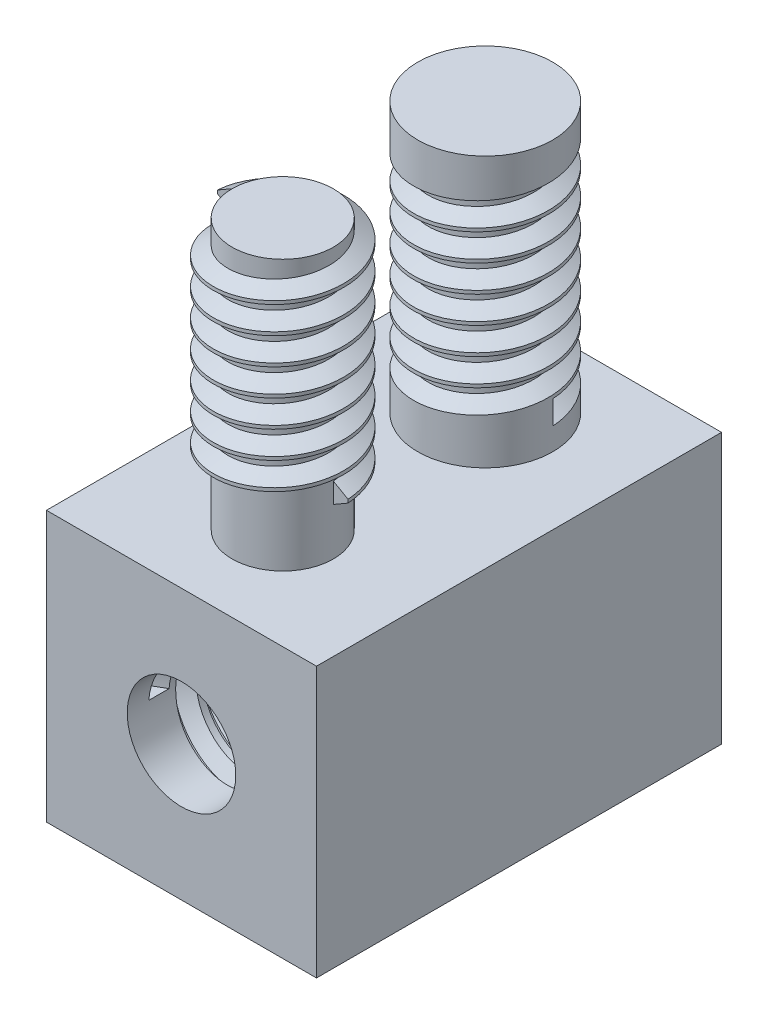
SolidWorks part; units mm, degrees
other "DetailItem1"
other "DetailItem2"
other "DetailItem3"
material "PEI"
ref_plane "Front Plane" through (0, 0, 0) normal (0, 0, 1) x (1, 0, 0)
ref_plane "Top Plane" through (0, 0, 0) normal (0, 1, 0) x (1, 0, 0)
ref_plane "Right Plane" through (0, 0, 0) normal (1, 0, 0) x (0, 0, -1)
sketch "Base Sketch" plane through (0, 0, 0) normal (0, 1, 0) x (1, 0, 0)
  line L1 (-6.35, -9.525) -> (6.35, -9.525)
  line L2 (-6.35, -9.525) -> (-6.35, 9.525)
  line L3 (-6.35, 9.525) -> (6.35, 9.525)
  line L4 (6.35, -9.525) -> (6.35, 9.525)
  line L5 (-6.35, -9.525) -> (6.35, 9.525) construction
  line L6 (-6.35, 9.525) -> (6.35, -9.525) construction
  point P0 (0, 0)
  dimension "D1" = 19.05
  dimension "D2" = 12.7
extrude "Base" add sketch "Base Sketch" along normal blind 12.7
sketch "Tower Sketch" plane through (0, 12.7, 0) normal (0, 1, 0) x (1, 0, 0)
  line L0 (0, 4.7625) -> (0, -4.7625) construction
  circle A0 centre (0, -4.7625) radius 2.3813
  circle A1 centre (0, 4.7625) radius 3.175
  dimension "D1" = 4.7625
  dimension "D2" = 6.35
  dimension "D3" = 9.525
extrude "Towers" add sketch "Tower Sketch" along normal blind 12.7
hole_wizard "1/4-20 Center Hole" positions "Hole Width" profile "Hole Depth" tap size "1/4-20" standard "ANSI Inch" end condition through all
sketch "Hole Width" plane through (0, 0, 9.525) normal (0, 0, 1) x (1, 0, 0)
  line L0 (-6.35, 0) -> (6.35, 12.7) construction
  point P0 (0, 6.35)
sketch "Hole Depth" plane through (0, 6.35, 9.525) normal (1, 0, 0) x (0, -1, 0)
  line L0 (0, 0) -> (0, 19.05)
  line L1 (0, 19.05) -> (2.5527, 19.05)
  line L2 (2.5527, 19.05) -> (2.5527, 0)
  line L5 (2.5527, 0) -> (0, 0)
  line L11 (0, -6.35) -> (0, 107.95) construction
  dimension "Thread Major Dia." = 5.1054
  dimension "Thru Tap Drill Depth" = 19.05
thread "Blue Thread" pitch 1.27 method extrude profile "Blue Thread Profile" start angle 0, offset 0, length 9.525, pitch 1.27, diameter 4.7625
ref_plane "Plane1" through (-2.3812, 25.4, 4.7625) normal (0, 0, 1) x (-1, 0, 0)
sketch "Blue Thread Profile" plane through (-2.3812, 25.4, 4.7625) normal (0, 0, 1) x (-1, 0, 0)
  line L0 (0, 0) -> (0, 1.27) construction
  line L1 (0, 0) -> (0.6874, 0.3969)
  line L2 (0.6874, 0.3969) -> (0.6874, 0.5556)
  line L3 (0.6874, 0.5556) -> (0, 0.9525)
  line L4 (0.6874, 0.4762) -> (0, 0.4762) construction
  line L11 (0, 0) -> (0, 0.9525)
  point P2 (0, 0)
  dimension "Pitch" = 1.27
  dimension "Profile_Angle" = 60
  dimension "Profile_Land" = 0.1588
  dimension "Profile_Height" = 0.6874
thread "Green Thread" pitch 1.27 method cut profile "Green Thread Profile" start angle 0, offset 1.016, length 9.525, pitch 1.27, diameter 6.35
ref_plane "Plane2" through (-3.175, 24.384, -4.7625) normal (0, 0, 1) x (-1, 0, 0)
sketch "Green Thread Profile" plane through (-3.175, 24.384, -4.7625) normal (0, 0, 1) x (-1, 0, 0)
  line L0 (0, 0) -> (0, 1.27) construction
  line L11 (0, 0) -> (0, 1.1112)
  line L12 (0, 1.1112) -> (-0.6874, 0.7144)
  line L13 (-0.6874, 0.7144) -> (-0.6874, 0.3969)
  line L15 (-0.6874, 0.3969) -> (0, 0)
  line L17 (-0.6874, 0.5556) -> (0, 0.5556) construction
  point P2 (0, 0)
  dimension "Pitch" = 1.27
  dimension "Profile_Angle" = 60
  dimension "Profile_Land" = 0.3175
  dimension "Profile_Height" = 0.6874
thread "Center Thread" pitch 1.27 method cut profile "Center Thread Profile" start angle 0, offset 1.016, length 0, pitch 1.27, diameter 5.1054
ref_plane "Plane3" through (-2.5527, 6.35, 8.509) normal (0, -1, 0) x (-1, 0, 0)
sketch "Center Thread Profile" plane through (-2.5527, 6.35, 8.509) normal (0, -1, 0) x (-1, 0, 0)
  line L0 (0, 0) -> (0, 1.27) construction
  line L1 (0, 0) -> (0.6874, 0.3969)
  line L2 (0.6874, 0.3969) -> (0.6874, 0.5556)
  line L3 (0.6874, 0.5556) -> (0, 0.9525)
  line L4 (0.6874, 0.4762) -> (0, 0.4762) construction
  line L11 (0, 0) -> (0, 0.9525)
  point P2 (0, 0)
  dimension "Pitch" = 1.27
  dimension "Profile_Angle" = 60
  dimension "Profile_Land" = 0.1588
  dimension "Profile_Height" = 0.6874
